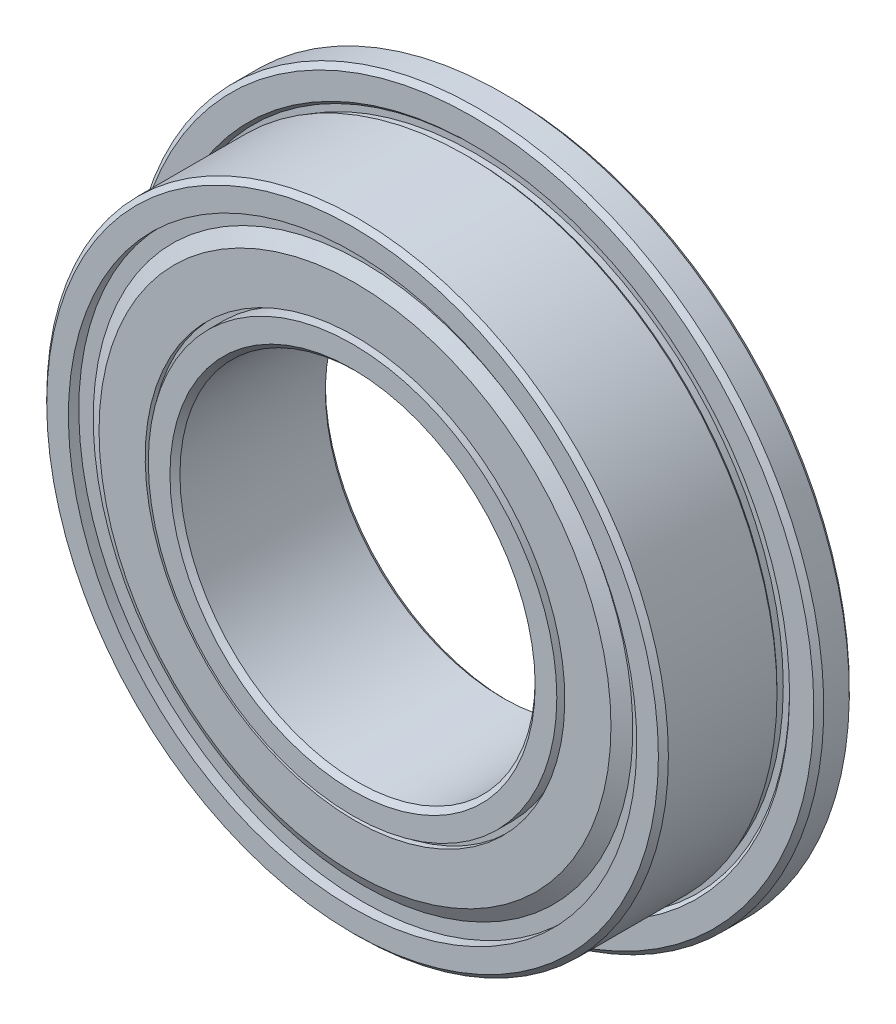
SolidWorks part; units mm, degrees
ref_plane "Front Plane" through (0, 0, 0) normal (0, 0, 1) x (1, 0, 0)
ref_plane "Top Plane" through (0, 0, 0) normal (0, 1, 0) x (1, 0, 0)
ref_plane "Right Plane" through (0, 0, 0) normal (1, 0, 0) x (0, 0, -1)
sketch "Sketch1" plane through (0, 0, 0) normal (1, 0, 0) x (0, 0, -1)
  line L0 (0, 7) -> (0, -7) construction
  line L1 (-1.75, 7) -> (1.75, 7) construction
  line L2 (0, 0) -> (1.75, 0) construction
  line L3 (1.75, 7.8) -> (1.75, -7.8) construction
  line L4 (1.75, -7.8) -> (0.95, -7.8) construction
  line L5 (1.75, 4) -> (0, 4) construction
  line L6 (1.75, 4) -> (1.75, -4) construction
  dimension "OD" = 14
  dimension "Width" = 3.5
  dimension "Flange Dia." = 15.6
  dimension "Flange Thickness" = 0.8
  dimension "ID" = 8
sketch "Sketch2" plane through (0, 0, 0) normal (1, 0, 0) x (0, 0, -1)
  line L0 (1.75, 7.8) -> (0.95, 7.8)
  line L1 (0.95, 7.8) -> (0.95, 7.1414)
  line L2 (0.8086, 7) -> (-1.75, 7)
  line L3 (-1.75, 7) -> (-1.75, 6.1)
  line L4 (-1.75, 6.1) -> (-0.45, 6.1)
  line L5 (1.75, 7.8) -> (1.75, -7.8) construction
  line L6 (1.75, 6.1) -> (1.75, 7.8)
  line L7 (1.75, 4) -> (-1.75, 4)
  line L8 (-1.75, 4) -> (-1.75, 4.9)
  line L9 (-1.75, 4.9) -> (-0.45, 4.9)
  line L10 (1.75, 4.9) -> (1.75, 4)
  line L11 (0, 7) -> (0, 4) construction
  line L12 (-0.75, 5.5) -> (0.75, 5.5) construction
  line L13 (0.45, 6.1) -> (1.75, 6.1)
  line L14 (0.45, 4.9) -> (1.75, 4.9)
  line L15 (0.95, 7.1414) -> (1.0207, 7.0707)
  line L16 (1.0207, 7.0707) -> (1.0207, 6.9293)
  line L17 (1.0207, 6.9293) -> (0.8793, 6.9293)
  line L18 (0.8793, 6.9293) -> (0.8086, 7)
  line L19 (0.95, 7) -> (1.0207, 6.9293) construction
  line L20 (1.0207, 7.0707) -> (0.8793, 6.9293) construction
  line L21 (0.8086, 7) -> (0.95, 7) construction
  line L22 (0.95, 7) -> (0.95, 7.1414) construction
  circle A0 centre (0, 5.5) radius 0.75 construction
  arc A1 (-0.45, 6.1) -> (0.45, 6.1) centre (0, 5.5) cw
  arc A2 (-0.45, 4.9) -> (0.45, 4.9) centre (0, 5.5) ccw
  dimension "D1" = 3
  dimension "Ball Dia." = 1.5
  dimension "D2" = 135
  dimension "D3" = 0.2
  dimension "D4" = 1.2
  dimension "Race Thikness" = 0.9
revolve "Revolve1" add sketch "Sketch2" angle 360 about L2
fillet "Fillet1" radius 0.1125 3 edges at (0, -7.8, -1.75) (0, -7.8, -0.95) (0, -7, 1.75) profile chamfer
sketch "Sketch3" plane through (0, 0, 0) normal (0, 0, 1) x (1, 0, 0)
  line L0 (-4, 0) -> (4, 0) construction
  line L1 (-7, 0) -> (7, 0) construction
  point P5 (0, 0)
  dimension "ID2" = 8
  dimension "OD2" = 14
fillet "Fillet2" radius 0.1125 2 edges at (0, -4, -1.75) (0, -4, 1.75) profile chamfer
sketch "Sketch7" plane through (0, 0, 0) normal (0, 0, 1) x (1, 0, 0)
  line L0 (0, 6.25) -> (0, 4.75)
  line L1 (0, 7.8) -> (0, -7.8) construction
  line L2 (-0.8603, 6.25) -> (0, 0) construction
  line L3 (0, 0) -> (0.8603, 6.25) construction
  line L4 (0.8603, 6.25) -> (-0.8603, 6.25) construction
  circle A0 centre (0, 5.5) radius 0.75 construction
  circle A1 centre (0, 0) radius 6.25 construction
  circle A2 centre (0, 0) radius 4.75 construction
  arc A4 (0, 6.25) -> (0, 4.75) centre (0, 5.5) ccw
  dimension "D1" = 15.675
revolve "Revolve3" add sketch "Sketch7" angle 360 about L0
pattern_circular "CirPattern3" count 19 over 360 about axis through (0, 0, 0) along (0, 0, -1) of bodies 107
sketch "Sketch8" plane through (0, 0, 0) normal (1, 0, 0) x (0, 0, -1)
  line L1 (-1.75, 6.1) -> (-1.39, 6.1)
  line L2 (-1.75, 6.1) -> (-1.75, 6.4)
  line L3 (-1.75, 6.4) -> (-1.39, 6.4)
  line L4 (-1.39, 6.1) -> (-1.39, 6.4)
  line L5 (1.75, 6.1) -> (1.39, 6.1)
  line L6 (1.75, 6.1) -> (1.75, 6.4)
  line L7 (1.75, 6.4) -> (1.39, 6.4)
  line L8 (1.39, 6.1) -> (1.39, 6.4)
  line L9 (1.75, 4.9) -> (1.39, 4.9)
  line L10 (1.75, 4.9) -> (1.75, 4.6)
  line L11 (1.75, 4.6) -> (1.39, 4.6)
  line L12 (1.39, 4.9) -> (1.39, 4.6)
  line L13 (-1.75, 4.9) -> (-1.39, 4.9)
  line L14 (-1.75, 4.9) -> (-1.75, 4.6)
  line L15 (-1.75, 4.6) -> (-1.39, 4.6)
  line L16 (-1.39, 4.9) -> (-1.39, 4.6)
  dimension "D1" = 0.3
  dimension "D2" = 0.36
revolve "Cut-Revolve1" cut sketch "Sketch8" angle 360 about L2
sketch "Sketch9" plane through (0, 0, 0) normal (1, 0, 0) x (0, 0, -1)
  line L0 (-1.39, 6.4) -> (-1.39, 6.0429)
  line L1 (-1.39, 6.0429) -> (-1.57, 5.7311)
  line L2 (-1.57, 5.7311) -> (-1.57, 4.725)
  line L3 (1.57, 4.725) -> (1.57, 4.6) construction
  line L4 (1.39, 6.4) -> (1.39, 6.0429)
  line L5 (1.39, 6.0429) -> (1.57, 5.7311)
  line L6 (1.57, 5.7311) -> (1.57, 4.725)
  line L7 (1.75, 4.6) -> (1.39, 4.6) construction
  line L8 (-1.515, 6.4) -> (-1.515, 6.0764)
  line L9 (-1.515, 6.0764) -> (-1.695, 5.7646)
  line L10 (-1.695, 5.7646) -> (-1.695, 4.725)
  line L11 (-1.39, 6.4) -> (-1.515, 6.4)
  line L12 (-1.57, 4.725) -> (-1.695, 4.725)
  line L13 (1.515, 6.4) -> (1.515, 6.0764)
  line L14 (1.515, 6.0764) -> (1.695, 5.7646)
  line L15 (1.695, 5.7646) -> (1.695, 4.725)
  line L16 (1.39, 6.4) -> (1.515, 6.4)
  line L17 (1.57, 4.725) -> (1.695, 4.725)
  line L18 (-1.39, 6.0429) -> (-1.39, 2.6) construction
  line L19 (1.39, 6.0429) -> (1.39, 6.4) construction
  line L20 (-1.39, 4.6) -> (-1.75, 4.6) construction
  line L22 (-1.57, 4.725) -> (-1.57, 4.6) construction
  dimension "D2" = 150
  dimension "D1" = 150
  dimension "D5" = 0.36
  dimension "D3" = 0.125
  dimension "D4" = 0.125
  dimension "D6" = 0.3571
revolve "Revolve4" add sketch "Sketch9" angle 360 about L2
ref_axis "Center Axis 1" through (0, 0, -0.66) along (0, 0, 1)
ref_plane "Contact Plane 1" through (0, 0, -0.95) normal (0, 0, 1) x (1, 0, 0)
equation "\"Ball Dia.@Sketch2\"=\"D1@Sketch2\"*.5"
equation "\"D3@Sketch2\"=\"Flange Thickness@Sketch1\"/4"
equation "\"D1@Fillet1\"=\"Race Thikness@Sketch2\"/8"
equation "\"ID2@Sketch3\" = \"ID@Sketch1\""
equation "\"OD2@Sketch3\" = \"OD@Sketch1\""
equation "\"D1@Fillet2\"=\"Race Thikness@Sketch2\"/8"
equation "\"D1@CirPattern3\"=360/\"D1@Sketch7\"-4"
equation "\"D1@Sketch8\"=\"Race Thikness@Sketch2\"/3"
equation "\"D2@Sketch8\"=\"Race Thikness@Sketch2\"/2.5"
equation "\"D3@Sketch9\"=\"D5@Sketch9\"/4"
equation "\"D4@Sketch9\"=\"D5@Sketch9\"/4"
equation "\"D1@Sketch9\"=\"D2@Sketch9\""
equation "\"D4@Sketch2\"=\"D1@Sketch2\"*.4"
